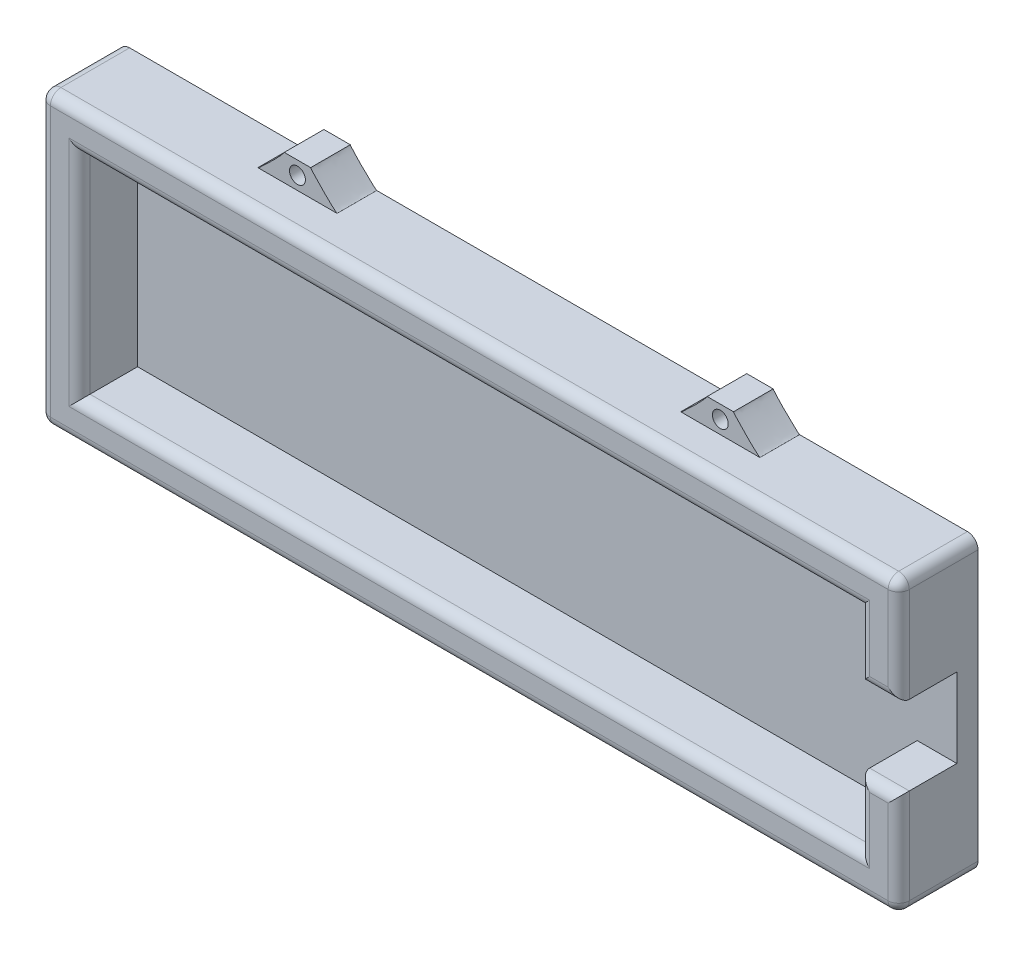
SolidWorks part; units mm, degrees
ref_plane "Piano frontale" through (0, 0, 0) normal (0, 0, 1) x (1, 0, 0)
ref_plane "Piano superiore" through (0, 0, 0) normal (0, 1, 0) x (1, 0, 0)
ref_plane "Piano destro" through (0, 0, 0) normal (1, 0, 0) x (0, 0, -1)
sketch "Schizzo1" plane through (0, 0, 0) normal (0, 0, 1) x (1, 0, 0)
  line L1 (-162.5, 55) -> (162.5, 55)
  line L2 (-162.5, 55) -> (-162.5, -55)
  line L3 (-162.5, -55) -> (162.5, -55)
  line L4 (162.5, 55) -> (162.5, -55)
  line L5 (-162.5, 55) -> (162.5, -55) construction
  line L6 (-162.5, -55) -> (162.5, 55) construction
  point P0 (0, 0)
  dimension "D1" = 325
  dimension "D2" = 110
extrude "Estrusione-Estrusione1" add sketch "Schizzo1" along normal blind 30
sketch "Schizzo2" plane through (0, 0, 30) normal (0, 0, 1) x (1, 0, 0)
  line L0 (162.5, -55) -> (162.5, 55) construction
  line L1 (-147.5, 40) -> (147.5, 40)
  line L2 (-147.5, 40) -> (-147.5, -40)
  line L3 (-147.5, -40) -> (147.5, -40)
  line L4 (147.5, 40) -> (147.5, -40)
  line L5 (-147.5, 40) -> (147.5, -40) construction
  line L6 (-147.5, -40) -> (147.5, 40) construction
  line L7 (147.5, 15) -> (162.5, 15)
  line L8 (147.5, 15) -> (147.5, -15)
  line L9 (147.5, -15) -> (162.5, -15)
  line L10 (162.5, 15) -> (162.5, -15)
  point P0 (0, 0)
  point P12 (147.5, 0)
  point P13 (147.5, 0)
  line M5 (162.5, -55) -> (162.5, 55)
  dimension "D1" = 295
  dimension "D2" = 80
  dimension "D3" = 30
extrude "Taglio-Estrusione1" cut sketch "Schizzo2" against normal offset from surface (22 mm away) 8 contours L4 L9 L7 M5 | L4 L1 L2 L3 region at (0, 0, 30) region at (155, 0, 30) up to face at (0, 0, 0)
sketch "Schizzo3" plane through (0, 0, 30) normal (0, 0, 1) x (1, 0, 0)
  line L0 (-162.5, 0) -> (216.1123, 0) construction
  line L1 (-162.5, 55) -> (-162.5, -55) construction
  line L2 (162.5, 55) -> (-162.5, 55) construction
  line L3 (-85, 55) -> (-75, 55)
  line L4 (-85, 55) -> (-85, 65)
  line L5 (-85, 65) -> (-75, 65)
  line L6 (-75, 55) -> (-75, 65)
  line L7 (0, 0) -> (0, 106.917) construction
  line L8 (85, 65) -> (75, 65)
  line L9 (85, 55) -> (85, 65)
  line L10 (85, 55) -> (75, 55)
  line L11 (75, 55) -> (75, 65)
  line L12 (85, -55) -> (85, -65)
  line L13 (85, -55) -> (75, -55)
  line L14 (75, -55) -> (75, -65)
  line L15 (85, -65) -> (75, -65)
  line L16 (-85, -65) -> (-75, -65)
  line L17 (-75, -55) -> (-75, -65)
  line L18 (-85, -55) -> (-75, -55)
  line L19 (-85, -55) -> (-85, -65)
  circle A0 centre (-80, 60) radius 3
  circle A1 centre (80, 60) radius 3
  circle A2 centre (80, -60) radius 3
  circle A3 centre (-80, -60) radius 3
  point P12 (-85, 60)
  point P13 (-80, 65)
  dimension "D1" = 10
  dimension "D2" = 6
  dimension "D3" = 80
extrude "Estrusione-Estrusione2" add sketch "Schizzo3" against normal up to surface (30 mm away) from offset 15 up to face at (0, 0, 0) offset against normal yes
fillet "Raccordo1" radius 10 8 edges at (85, 55, 7.5) (-75, 55, 7.5) (75, 55, 7.5) (-85, 55, 7.5) (75, -55, 7.5) (85, -55, 7.5) (-75, -55, 7.5) (-85, -55, 7.5) conic rho 0.05
fillet "Raccordo2" radius 4 16 edges at (0, 40, 30) (-147.5, 0, 30) (0, -40, 30) (147.5, -27.5, 30) (155, -15, 30) (162.5, -35, 30) (0, -55, 30) (-162.5, 0, 30) (0, 55, 30) (162.5, 35, 30) (155, 15, 30) (147.5, 27.5, 30) (-162.5, 55, 15) (-162.5, -55, 15) (162.5, -55, 15) (162.5, 55, 15)
